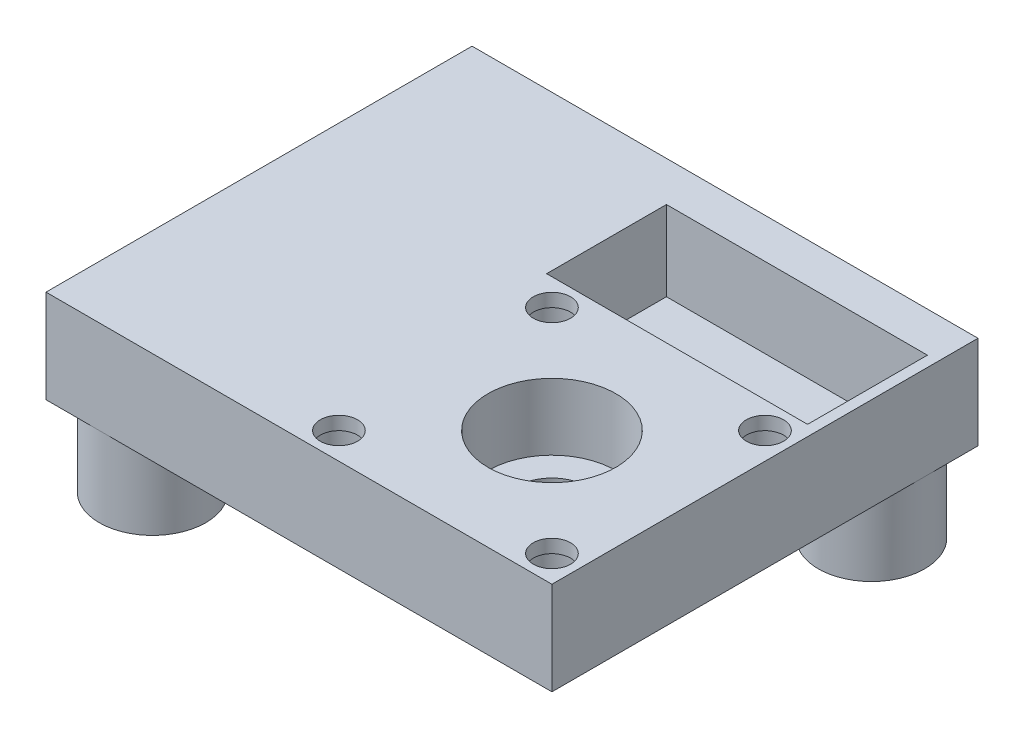
SolidWorks part; units mm, degrees
ref_plane "前视基准面" through (0, 0, 0) normal (0, 0, 1) x (1, 0, 0)
ref_plane "上视基准面" through (0, 0, 0) normal (0, 1, 0) x (1, 0, 0)
ref_plane "右视基准面" through (0, 0, 0) normal (1, 0, 0) x (0, 0, -1)
other "Configuration Table"
sketch "草图1" plane through (0, 0, 0) normal (0, 1, 0) x (1, 0, 0)
  line L0 (3, 3) -> (5, 5)
  line L1 (-5, 5) -> (5, 5)
  line L2 (-5, 5) -> (-5, -5)
  line L3 (-5, -5) -> (5, -5)
  line L4 (5, 5) -> (5, -5)
  line L5 (-5, 5) -> (5, -5) construction
  line L6 (-5, -5) -> (5, 5) construction
  line L7 (-3, 3) -> (3, 3)
  line L8 (-3, 3) -> (-3, -3)
  line L9 (-3, -3) -> (3, -3)
  line L10 (3, 3) -> (3, -3)
  line L11 (-3, 3) -> (3, -3) construction
  line L12 (-3, -3) -> (3, 3) construction
  line L13 (-3, -3) -> (-5, -5)
  line L15 (-5, 11) -> (5, 11)
  line L16 (-5, 11) -> (-5, 5)
  line L17 (-5, 5) -> (5, 5)
  line L18 (5, 11) -> (5, 5)
  line L19 (-14, 11) -> (-5, 11)
  line L20 (-14, 11) -> (-14, -5)
  line L21 (-14, -5) -> (-5, -5)
  line L22 (-5, 11) -> (-5, -5)
  circle A0 centre (0, 0) radius 2.4
  circle A1 centre (0, 0) radius 1.35
  circle A2 centre (4, 4) radius 0.95
  circle A3 centre (4, 4) radius 0.7
  circle A4 centre (-4, -4) radius 0.95
  circle A5 centre (-4, -4) radius 0.7
  circle A6 centre (-4, 4) radius 0.95
  circle A7 centre (-4, 4) radius 0.7
  circle A8 centre (4, -4) radius 0.95
  circle A9 centre (4, -4) radius 0.7
  circle A10 centre (-3.9, 6.4) radius 1.25
  dimension "D2" = 4.8
  dimension "D5" = 2.7
  dimension "D6" = 2.5
  dimension "D10" = 9
  dimension "D11" = 1.4
  dimension "D9" = 6
  dimension "D13" = 1.9
  dimension "D3" = 10
  dimension "D4" = 6
  dimension "D7" = 6.4
  dimension "D8" = 3.9
extrude "凸台-拉伸1" add sketch "草图1" along normal blind 3.5 contours L1 L4 L3 L2 | L18 L17 L16 L15 | L19 L22 L21 L20
extrude "切除-拉伸1" cut sketch "草图1<3>" along normal through all contours A1 region at (0, 0, 0)
sketch "草图1<3>" plane through (0, 0, 0) normal (0, 1, 0) x (1, 0, 0) same geometry as "草图1"
extrude "切除-拉伸2" cut sketch "草图1<4>" against normal blind 2.5 from surface contours A0 A1 region at (-2.3321, 0, 0) starting at face at (0, 3.5, 1.35)
sketch "草图1<4>" plane through (0, 0, 0) normal (0, 1, 0) x (1, 0, 0) same geometry as "草图1"
extrude "切除-拉伸3" cut sketch "草图1<7>" along normal through all contours A7 | A3 | A5 | A9
sketch "草图1<7>" plane through (0, 0, 0) normal (0, 1, 0) x (1, 0, 0) same geometry as "草图1"
extrude "切除-拉伸8" cut sketch "草图1<18>" along normal blind 3 contours A4 | A8 | A2 | A6
sketch "草图1<18>" plane through (0, 0, 0) normal (0, 1, 0) x (1, 0, 0) same geometry as "草图1"
extrude "切除-拉伸4" cut sketch "草图1<17>" along normal through all contours A10
sketch "草图1<17>" plane through (0, 0, 0) normal (0, 1, 0) x (1, 0, 0) same geometry as "草图1"
sketch "草图2" plane through (0, 3.5, 0) normal (0, 1, 0) x (1, 0, 0)
  line L0 (-5, 5) -> (5, 5) construction
  line L1 (-5.2, 9.5) -> (4.6, 9.5)
  line L2 (-5.2, 9.5) -> (-5.2, 5)
  line L3 (-5.2, 5) -> (4.6, 5)
  line L4 (4.6, 9.5) -> (4.6, 5)
extrude "切除-拉伸5" cut sketch "草图2" against normal blind 3
sketch "草图4" plane through (0, 0, 0) normal (0, -1, 0) x (1, 0, 0)
  circle A0 centre (-8.1071, -2.5542) radius 1.05
  dimension "D1" = 2.1
extrude "切除-拉伸6" cut sketch "草图4" against normal blind 2.8
sketch "草图5" plane through (0, 0, 0) normal (0, -1, 0) x (1, 0, 0)
  line L0 (-14, 5) -> (5, 5) construction
  line L1 (-14, -11) -> (-14, 5) construction
  line L2 (-14, -11) -> (5, -11) construction
  line L3 (5, -11) -> (5, 5) construction
  circle A0 centre (-12, 3) radius 2
  circle A1 centre (-12, -9) radius 2
  circle A2 centre (3, -9) radius 2
  circle A3 centre (3, -9) radius 0.3
  circle A4 centre (-12, -9) radius 0.3
  circle A5 centre (-12, 3) radius 0.3
  dimension "D1" = 0.6
  dimension "D2" = 4
extrude "凸台-拉伸2" add sketch "草图5" along normal blind 3 contours A0 | A1 | A2
extrude "切除-拉伸7" cut sketch "草图5<3>" against normal blind 1.5 from surface contours A4 | A5 | A3 starting at face at (3, -3, -11)
sketch "草图5<3>" plane through (0, 0, 0) normal (0, -1, 0) x (1, 0, 0) same geometry as "草图5"
